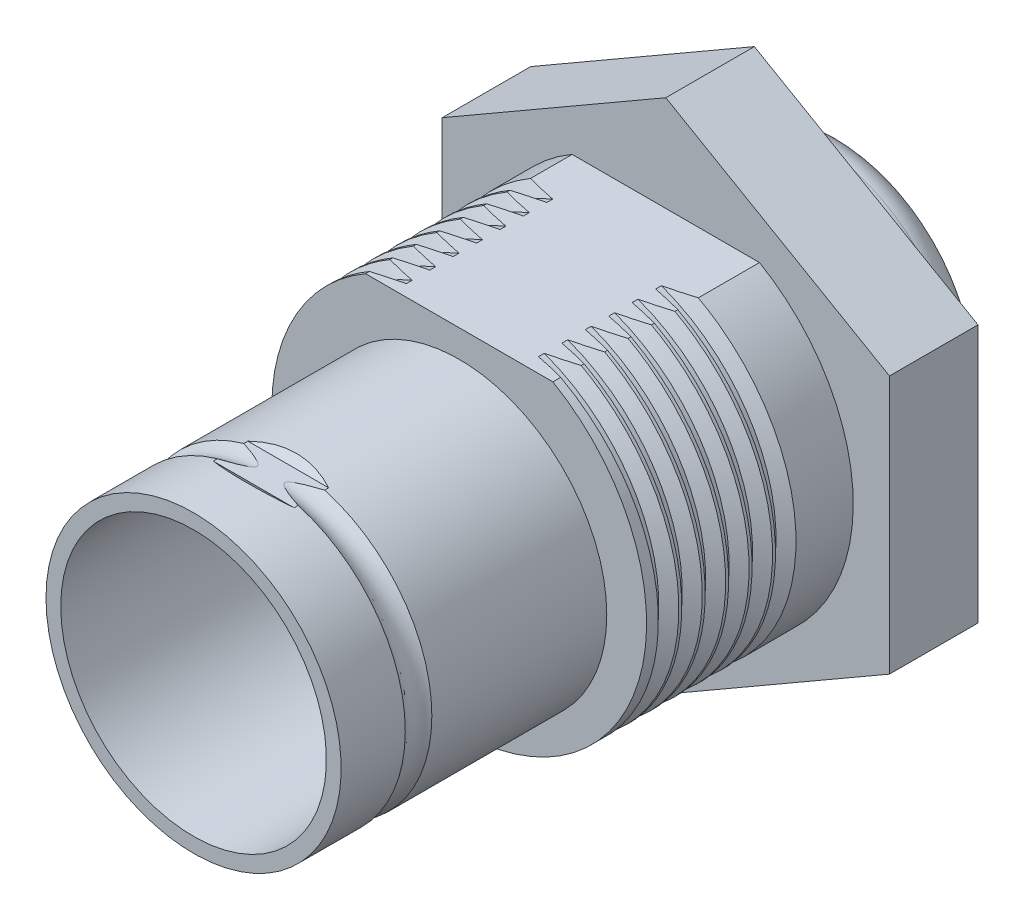
SolidWorks part; units mm, degrees
ref_plane "Front Plane" through (0, 0, 0) normal (0, 0, 1) x (1, 0, 0)
ref_plane "Top Plane" through (0, 0, 0) normal (0, 1, 0) x (1, 0, 0)
ref_plane "Right Plane" through (0, 0, 0) normal (1, 0, 0) x (0, 0, -1)
sketch "Sketch1" plane through (0, 0, 0) normal (0, 0, 1) x (1, 0, 0)
  line L1 (0, -8.75) -> (7.5777, -4.375)
  line L2 (7.5777, -4.375) -> (7.5777, 4.375)
  line L3 (7.5777, 4.375) -> (0, 8.75)
  line L4 (0, 8.75) -> (-7.5777, 4.375)
  line L5 (-7.5777, 4.375) -> (-7.5777, -4.375)
  line L6 (-7.5777, -4.375) -> (0, -8.75)
  circle A0 centre (0, 0) radius 7.5777 construction
  dimension "D1" = 17.5
extrude "Boss-Extrude1" add sketch "Sketch1" along normal blind 3
sketch "Sketch2" plane through (0, 0, 3) normal (0, 0, 1) x (1, 0, 0)
  line L0 (-3.1737, 5.5) -> (3.1737, 5.5)
  arc A0 (-3.1737, 5.5) -> (3.1737, 5.5) centre (0, 0) ccw
  dimension "D1" = 12.7
  dimension "D2" = 5.5
extrude "Boss-Extrude2" add sketch "Sketch2" along normal blind 7
sketch "Sketch3" plane through (0, 0, 0) normal (1, 0, 0) x (0, 0, -1)
  line L0 (-10, 4.575) -> (-19, 4.575)
  line L1 (-10, 5.5) -> (-10, -6.35) construction
  line L2 (-19, 4.575) -> (-19, 4.075)
  line L3 (-19, 4.075) -> (-10, 4.075)
  line L5 (-10, 4.075) -> (-10, 4.575)
  line L6 (-10, -0.425) -> (-22.5021, -0.425) construction
  dimension "D1" = 9
  dimension "D2" = 0.5
  dimension "D3" = 5
revolve "Revolve3" add sketch "Sketch3" angle 360 about L6
sketch "Sketch5" plane through (0, 0, 0) normal (1, 0, 0) x (0, 0, -1)
  line L0 (-3, -0.425) -> (-21.4903, -0.425) construction
  line L1 (-3, 5.5) -> (-3, -6.35) construction
  circle A0 centre (-16.3768, 5.0945) radius 0.6874
revolve "Cut-Revolve1" cut sketch "Sketch5" angle 360 about L0
sketch "Sketch6" plane through (0, 0, 0) normal (1, 0, 0) x (0, 0, -1)
  line L0 (-17.2208, 4.575) -> (-16.9637, 4.3839)
  line L3 (-16.9637, 4.3839) -> (-15.792, 4.3839)
  line L4 (-15.792, 4.3839) -> (-15.5161, 4.575)
  line L5 (-10, 4.575) -> (-15.9267, 4.575) construction
  line L6 (-15.5161, 4.575) -> (-15.5161, 5.1759)
  line L7 (-15.5161, 5.1759) -> (-17.2208, 5.1759)
  line L8 (-17.2208, 5.1759) -> (-17.2208, 4.575)
  line L9 (-10, -0.425) -> (-22.1734, -0.425) construction
  line L10 (-10, 4.075) -> (-10, -4.925) construction
  line L11 (-17.2208, -6.0259) -> (-17.2208, -5.425)
  line L12 (-15.5161, -6.0259) -> (-17.2208, -6.0259)
  line L13 (-15.5161, -5.425) -> (-15.5161, -6.0259)
  line L14 (-15.792, -5.2339) -> (-15.5161, -5.425)
  line L15 (-16.9637, -5.2339) -> (-15.792, -5.2339)
  line L16 (-17.2208, -5.425) -> (-16.9637, -5.2339)
extrude "Cut-Extrude1" cut sketch "Sketch6" against normal through all both and the other way through all
thread "Thread1" pitch 0.7937 method cut profile "Thread Profile1" start angle 0, offset 0, length 5, pitch 0.7937, diameter 12.7
ref_plane "Plane1" through (-6.35, 0, 10) normal (0, -1, 0) x (-1, 0, 0)
sketch "Thread Profile1" plane through (-6.35, 0, 10) normal (0, -1, 0) x (-1, 0, 0)
  line L0 (0, 0) -> (0, 0.7937) construction
  line L11 (0, 0) -> (0, 0.6945)
  line L12 (0, 0.6945) -> (-0.4296, 0.4465)
  line L13 (-0.4296, 0.4465) -> (-0.4296, 0.248)
  line L15 (-0.4296, 0.248) -> (0, 0)
  line L17 (-0.4296, 0.3473) -> (0, 0.3473) construction
  point P2 (0, 0)
  dimension "Pitch" = 0.7937
  dimension "Profile_Angle" = 60
  dimension "Profile_Land" = 0.1984
  dimension "Profile_Height" = 0.4296
sketch "Sketch14" plane through (0, 0, 0) normal (0, 0, -1) x (-1, 0, 0)
  circle A0 centre (0, 0) radius 5
  dimension "D1" = 10
extrude "Boss-Extrude3" add sketch "Sketch14" along normal blind 3
fillet "Fillet1" radius 1 1 edges at (-5, 0, -3)
